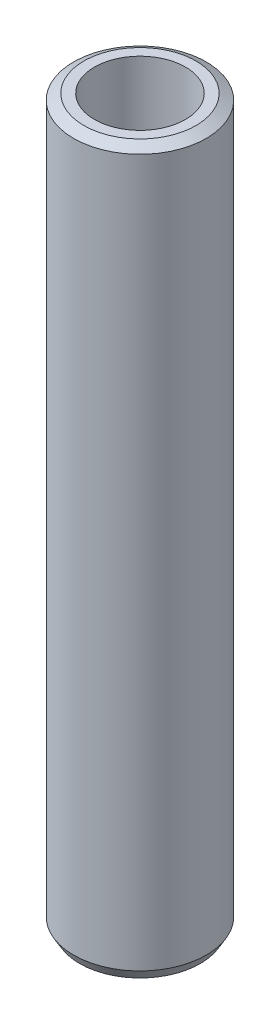
SolidWorks part; units mm, degrees
ref_plane "Front Plane" through (0, 0, 0) normal (0, 0, 1) x (1, 0, 0)
ref_plane "Top Plane" through (0, 0, 0) normal (0, 1, 0) x (1, 0, 0)
ref_plane "Right Plane" through (0, 0, 0) normal (1, 0, 0) x (0, 0, -1)
sketch "Sketch1" plane through (0, 0, 0) normal (0, 1, 0) x (1, 0, 0)
  circle A0 centre (0, 0) radius 55
  dimension "SHAFT_OD" = 110
extrude "Boss-Extrude1" add sketch "Sketch1" along normal blind 600
sketch "Sketch2" plane through (0, 0, 0) normal (0, 1, 0) x (1, 0, 0)
  circle A0 centre (0, 0) radius 37.712
  dimension "BORE_D" = 75.4241
extrude "Cut-Extrude1" cut sketch "Sketch2" along normal through all
chamfer "Chamfer1" distance 4.946 angle 60 2 edges at (0, 600, 55) (0, 0, 55) first distance on face at (0, 600, 55) first distance on face at (0, 0, 37.712)
